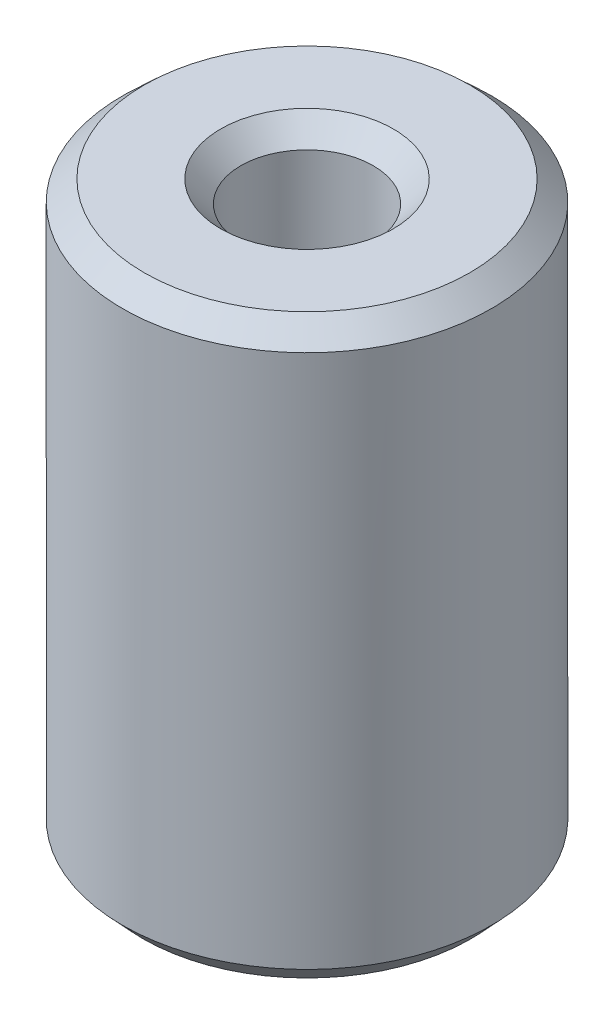
SolidWorks part; units mm, degrees
ref_plane "Front Plane" through (0, 0, 0) normal (0, 0, 1) x (1, 0, 0)
ref_plane "Top Plane" through (0, 0, 0) normal (0, 1, 0) x (1, 0, 0)
ref_plane "Right Plane" through (0, 0, 0) normal (1, 0, 0) x (0, 0, -1)
sketch "Sketch1" plane through (0, 0, 0) normal (0, 1, 0) x (1, 0, 0)
  circle A0 centre (0, 0) radius 15
  dimension "SLEEVE_OD" = 30
extrude "Boss-Extrude1" add sketch "Sketch1" along normal blind 46.8487
sketch "Sketch2" plane through (0, 0, 0) normal (0, 1, 0) x (1, 0, 0)
  circle A0 centre (0, 0) radius 5.3881
  dimension "BORE_D" = 10.7762
extrude "Cut-Extrude1" cut sketch "Sketch2" along normal through all
chamfer "Chamfer1" distance 1.6436 angle 47.028 4 edges at (0, 46.8487, 5.3881) (0, 0, 5.3881) (0, 0, 15) (0, 46.8487, 15) first distance on face at (0, 46.8487, 5.3881) first distance on face at (0, 0, 5.3881) first distance on face at (0, 46.8487, 15)
